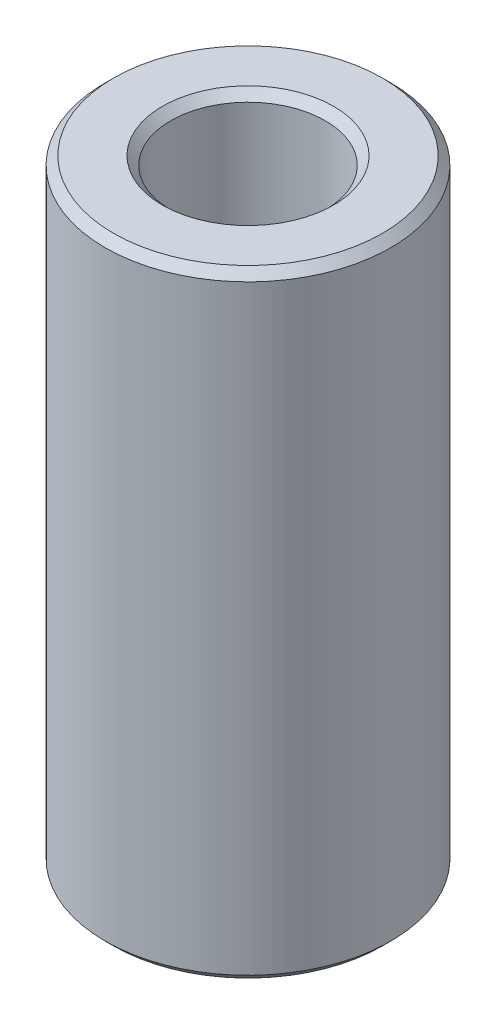
SolidWorks part; units mm, degrees
ref_plane "Front Plane" through (0, 0, 0) normal (0, 0, 1) x (1, 0, 0)
ref_plane "Top Plane" through (0, 0, 0) normal (0, 1, 0) x (1, 0, 0)
ref_plane "Right Plane" through (0, 0, 0) normal (1, 0, 0) x (0, 0, -1)
sketch "Sketch1" plane through (0, 0, 0) normal (0, 1, 0) x (1, 0, 0)
  circle A0 centre (0, 0) radius 25
  dimension "SLEEVE_OD" = 50
extrude "Boss-Extrude1" add sketch "Sketch1" along normal blind 108.0412
sketch "Sketch2" plane through (0, 0, 0) normal (0, 1, 0) x (1, 0, 0)
  circle A0 centre (0, 0) radius 13.5319
  dimension "BORE_D" = 27.0638
extrude "Cut-Extrude1" cut sketch "Sketch2" along normal through all
chamfer "Chamfer1" distance 1.4565 angle 45 4 edges at (0, 108.0412, 13.5319) (0, 0, 13.5319) (0, 0, 25) (0, 108.0412, 25)
